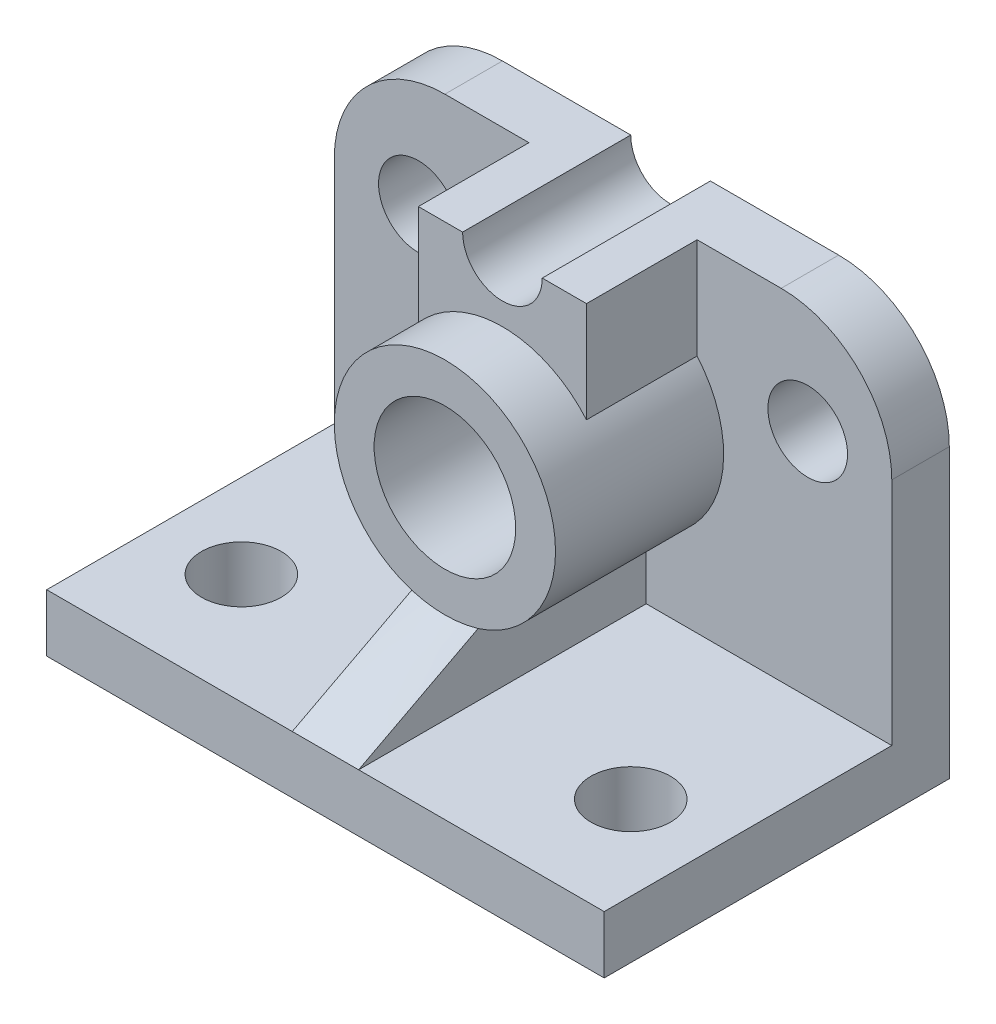
SolidWorks part; units mm, degrees
ref_plane "Front Plane" through (0, 0, 0) normal (0, 0, 1) x (1, 0, 0)
ref_plane "Top Plane" through (0, 0, 0) normal (0, 1, 0) x (1, 0, 0)
ref_plane "Right Plane" through (0, 0, 0) normal (1, 0, 0) x (0, 0, -1)
sketch "Sketch1" plane through (0, 0, 0) normal (0, 0, 1) x (1, 0, 0)
  line L0 (63, 0) -> (-63, 0)
  line L1 (0, 0) -> (0, 102) construction
  line L2 (-63, 0) -> (-63, 13)
  line L3 (-63, 13) -> (63, 13)
  line L4 (63, 13) -> (63, 0)
  line L5 (-63, 13) -> (-63, 90)
  line L6 (-63, 90) -> (-9, 90)
  line L7 (63, 90) -> (63, 13)
  line L8 (-19, 90) -> (-19, 67.2481)
  line L9 (19, 90) -> (19, 67.2481)
  line L10 (9, 90) -> (63, 90)
  circle A2 centre (0, 51) radius 16
  circle A3 centre (0, 51) radius 25
  arc A4 (9, 90) -> (-9, 90) centre (0, 90) cw
  point P2 (0, 13)
  point P4 (0, 0)
  dimension "D1" = 126
  dimension "D2" = 77
  dimension "D3" = 32
  dimension "D4" = 50
  dimension "D7" = 9
  dimension "D5" = 13
  dimension "D6" = 38
  dimension "D8" = 10
  dimension "D9" = 10
extrude "Boss-Extrude1" add sketch "Sketch1" along normal blind 78 contours L0 L1 L3 L2 | L1 L0 L4 L3 region at (31.5, 6.5, 0) region at (-31.5, 6.5, 0)
extrude "Boss-Extrude2" add sketch "Sketch1<3>" along normal blind 51 separate body contours A3 L1 A2 | L1 A3 A2 region at (-22.1991, 40.7745, 0) region at (0.559, 30.5, 0)
sketch "Sketch1<3>" plane through (0, 0, 0) normal (0, 0, 1) x (1, 0, 0) same geometry as "Sketch1"
extrude "Boss-Extrude3" add sketch "Sketch1<5>" along normal blind 13 contours L1 L3 L7 L10 L9 A3 | L3 L1 A3 L8 L6 L5 region at (39.1648, 48.9648, 0) region at (-39.1648, 48.9648, 0)
sketch "Sketch1<5>" plane through (0, 0, 0) normal (0, 0, 1) x (1, 0, 0) same geometry as "Sketch1"
extrude "Boss-Extrude5" add sketch "Sketch1<7>" along normal blind 38 contours A3 L1 A4 L6 L8 | L1 A3 L9 L10 A4 region at (11.9175, 80.2887, 0) region at (-11.9175, 80.2887, 0)
sketch "Sketch1<7>" plane through (0, 0, 0) normal (0, 0, 1) x (1, 0, 0) same geometry as "Sketch1"
fillet "Fillet1" radius 25 2 edges at (-63, 90, 6.5) (63, 90, 6.5)
sketch "Sketch2" plane through (0, 0, 0) normal (0, 0, 1) x (1, 0, 0)
  line L0 (-63, 13) -> (-63, 65) construction
  line L1 (0, 0) -> (0, 95.8402) construction
  line L2 (-38, 90) -> (-19, 90) construction
  circle A0 centre (-44, 65) radius 9
  circle A1 centre (44, 65) radius 9
  dimension "D2" = 18
  dimension "D1" = 19
  dimension "D3" = 25
sketch "Sketch3" plane through (0, 0, 0) normal (0, 1, 0) x (1, 0, 0)
  line L0 (-63, -78) -> (-63, -13) construction
  line L1 (0, 0) -> (0, -89.1051) construction
  line L2 (-63, -78) -> (63, -78) construction
  circle A0 centre (-44, -53) radius 9
  circle A1 centre (44, -53) radius 9
  dimension "D2" = 18
  dimension "D1" = 19
  dimension "D3" = 25
extrude "Cut-Extrude1" cut sketch "Sketch3" against normal through all both and the other way through all
extrude "Cut-Extrude2" cut sketch "Sketch2" against normal through all both and the other way through all
ref_plane "Plane1" through (7.5, 0, 0) normal (1, 0, 0) x (0, 0, -1)
ref_plane "Plane2" through (-7.5, 0, 0) normal (1, 0, 0) x (0, 0, -1)
sketch "Sketch5" plane through (0, 0, 0) normal (1, 0, 0) x (0, 0, -1)
  line L0 (-78, 13) -> (-51, 26.0661)
  line L1 (-51, 76) -> (-51, 26) construction
  line L2 (-51, 26.0661) -> (-13, 26)
  line L3 (-13, 26) -> (-13, 13)
  line L4 (-13, 13) -> (-78, 13)
sketch "Sketch7" plane through (7.5, 0, 0) normal (1, 0, 0) x (0, 0, -1)
  line L0 (-78, 13) -> (-51, 27.1515)
  line L3 (-51, 27.1515) -> (-13, 27.1515)
  line L4 (-13, 67.2481) -> (-13, 26) construction
  line L5 (-13, 27.1515) -> (-13, 13)
  line L6 (-13, 13) -> (-78, 13)
sketch "Sketch9" plane through (0, 0, 0) normal (1, 0, 0) x (0, 0, -1)
  line L0 (-51, 26) -> (-78, 13)
  line L1 (-78, 13) -> (-13, 13)
  line L2 (-13, 13) -> (-13, 26)
  line L3 (-13, 26) -> (-51, 26)
ref_plane "Plane3" through (7.5, 0, 0) normal (1, 0, 0) x (0, 0, -1)
ref_plane "Plane4" through (-7.5, 0, 0) normal (1, 0, 0) x (0, 0, -1)
sketch "Sketch12" plane through (7.5, 0, 0) normal (1, 0, 0) x (0, 0, -1)
  line L0 (-51, 27.1515) -> (-78, 13)
  line L1 (-78, 13) -> (-13, 13)
  line L2 (-51, 27.1515) -> (-13, 27.1515)
  line L3 (-13, 67.2481) -> (-13, 26) construction
  line L4 (-13, 27.1515) -> (-13, 13)
sketch "Sketch13" plane through (-7.5, 0, 0) normal (1, 0, 0) x (0, 0, -1)
  line L0 (-78, 13) -> (-13, 13) construction
  line L1 (-13, 27.1515) -> (-13, 13) construction
  line L2 (-51, 27.1515) -> (-13, 27.1515) construction
  line L3 (-51, 27.1515) -> (-78, 13) construction
  line L4 (-78, 13) -> (-13, 13)
  line L5 (-13, 27.1515) -> (-13, 13)
  line L6 (-51, 27.1515) -> (-13, 27.1515)
  line L7 (-51, 27.1515) -> (-78, 13)
loft "Loft1" add profiles "Sketch13", "Sketch5", "Sketch12" start constraint default end constraint default connector at (-7.5, 27.1515, 51) connector at (0, 26.0661, 51) connector at (7.5, 27.1515, 51)
